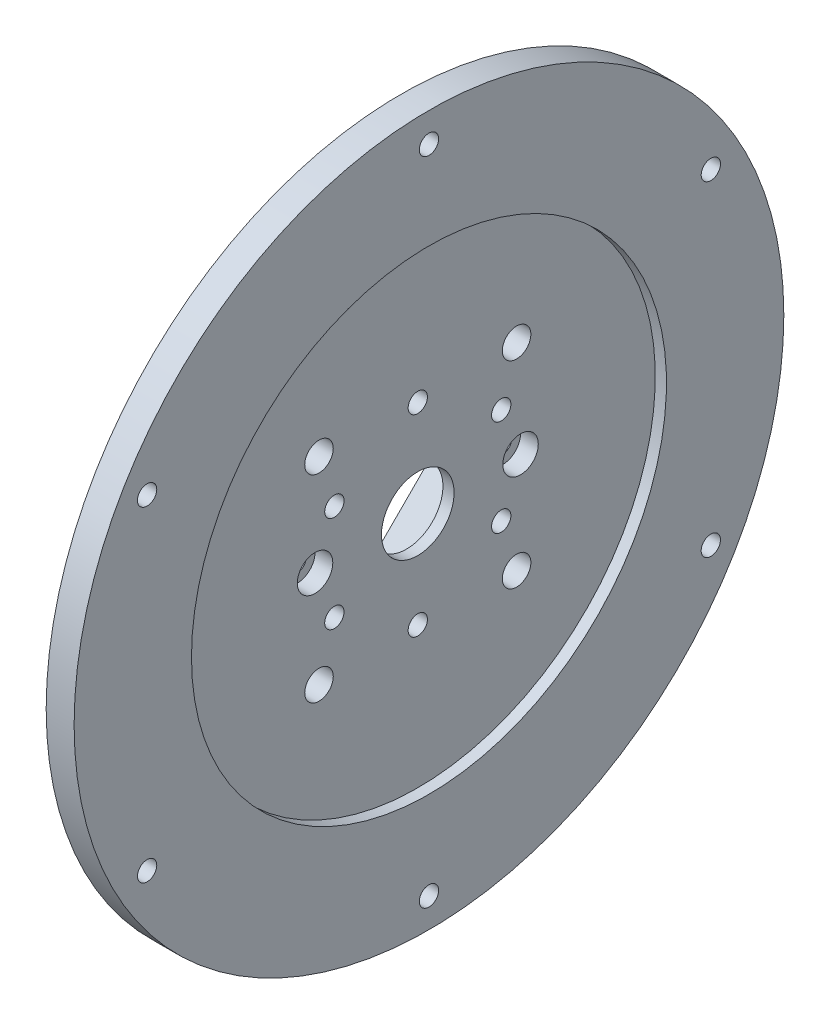
SolidWorks part; units mm, degrees
ref_plane "Front Plane" through (0, 0, 0) normal (0, 0, 1) x (1, 0, 0)
ref_plane "Top Plane" through (0, 0, 0) normal (0, 1, 0) x (1, 0, 0)
ref_plane "Right Plane" through (0, 0, 0) normal (1, 0, 0) x (0, 0, -1)
sketch "Sketch1" plane through (0, 0, 0) normal (0, 0, 1) x (1, 0, 0)
  line L0 (0, 0) -> (58.591, 0) construction
  line L2 (0, 0) -> (18.4, 0)
  line L3 (0, 0) -> (0, 2.5)
  line L4 (0, 2.5) -> (18.4, 2.5)
  line L5 (18.4, 0) -> (18.4, 2.5)
  line L6 (6, 2.5) -> (6, 6)
  line L11 (6, 6) -> (9.97, 6)
  line L16 (12.97, 6) -> (12.97, 3)
  line L17 (12.97, 3) -> (13.6304, 3)
  line L18 (13.6304, 3) -> (13.6304, 2.5)
  line L19 (13.6304, 2.5) -> (6, 2.5)
  line L22 (13.6304, 2.5) -> (16.1104, 2.5)
  line L23 (13.6304, 2.5) -> (13.6304, 4)
  line L24 (13.6304, 4) -> (16.1104, 4)
  line L25 (16.1104, 2.5) -> (16.1104, 4)
  line L27 (6, 6) -> (9.97, 6)
  line L28 (6, 6) -> (6, 9)
  line L29 (6, 9) -> (9.97, 9)
  line L30 (9.97, 6) -> (9.97, 9)
  line L31 (6, 9) -> (6, 8.25)
  line L32 (6, 8.25) -> (5, 8.25)
  line L33 (8.58, 22.001) -> (8.58, 12.476) construction
  line L34 (5, 12.476) -> (12.16, 12.476)
  line L35 (9.97, 9) -> (12.16, 9)
  line L36 (5, 7.5) -> (3, 7.5)
  line L37 (5, 8.25) -> (5, 12.476)
  line L38 (5, 7.5) -> (5, 14)
  line L39 (5, 14) -> (3, 14)
  line L40 (3, 7.5) -> (3, 14)
  line L41 (5, 22.001) -> (12.16, 22.001)
  line L42 (5, 22.001) -> (5, 30.1625)
  line L43 (5, 30.1625) -> (12.16, 30.1625)
  line L44 (12.16, 22.001) -> (12.16, 30.1625)
  line L49 (16.6304, 22.001) -> (16.6304, 7.5)
  line L51 (23.0104, 7.5) -> (23.0104, 6.5)
  line L54 (16.1104, 4) -> (13.6304, 4)
  line L56 (18.0304, 7.5) -> (23.0104, 7.5)
  line L57 (13.16, 22.001) -> (16.6304, 22.001)
  line L58 (16.1104, 3.5) -> (20.0104, 3.5)
  line L59 (29.9004, 14) -> (26.9004, 11)
  line L60 (4, 31.75) -> (18.0304, 31.75)
  line L61 (18.0304, 7.5) -> (23.0104, 7.5)
  line L62 (18.0304, 7.5) -> (18.0304, 12)
  line L63 (18.0304, 12) -> (23.0104, 12)
  line L64 (23.0104, 7.5) -> (23.0104, 12)
  line L65 (18.0304, 31.75) -> (18.0304, 12)
  line L66 (23.0104, 11) -> (26.9004, 11)
  line L67 (34.8004, 23) -> (31.3004, 19.5)
  line L68 (35.8004, 31) -> (38.7904, 33.99)
  line L69 (29.9004, 14) -> (29.9004, 15)
  line L70 (29.9004, 15) -> (22.9304, 15)
  line L71 (22.9304, 15) -> (21.0304, 15)
  line L72 (18.0304, 7.5) -> (16.6304, 7.5)
  line L73 (21.0304, 15) -> (21.0304, 43)
  line L74 (20.0304, 40) -> (10.0704, 40)
  line L75 (10.0704, 40) -> (4, 40)
  line L76 (21.0304, 43) -> (20.0304, 43)
  line L77 (22.9304, 15) -> (29.9004, 15)
  line L78 (22.9304, 15) -> (22.9304, 21)
  line L79 (22.9304, 21) -> (29.9004, 21)
  line L80 (29.9004, 15) -> (29.9004, 21)
  line L81 (10.0704, 40) -> (20.0304, 40)
  line L82 (10.0704, 40) -> (10.0704, 50)
  line L83 (10.0704, 50) -> (20.0304, 50)
  line L84 (20.0304, 40) -> (20.0304, 50)
  line L85 (4, 40) -> (4, 31.75)
  line L86 (12.97, 3) -> (12.97, 2.5)
  line L87 (31.3004, 19.5) -> (29.9004, 19.5)
  line L88 (21.51, 63.5) -> (21.51, 44)
  line L89 (21.51, 63.5) -> (25.9304, 63.5)
  line L90 (25.9304, 63.5) -> (25.9304, 25)
  line L91 (27.8304, 25) -> (25.9304, 25)
  line L92 (10.0704, 48) -> (9, 48)
  line L93 (9, 48) -> (9, 53.476)
  line L94 (9, 53.476) -> (20.0304, 53.476)
  line L95 (20.0304, 53.476) -> (20.0304, 50)
  line L96 (14.5152, 63.001) -> (14.5152, 53.476) construction
  line L97 (9, 63.001) -> (20.0304, 63.001)
  line L98 (9, 63.001) -> (9, 68.2625)
  line L99 (9, 68.2625) -> (20.0304, 68.2625)
  line L100 (20.0304, 63.001) -> (20.0304, 68.2625)
  line L101 (12.97, 6) -> (11.97, 6)
  line L102 (9, 42.5) -> (5, 42.5)
  line L103 (9, 42.5) -> (9, 55)
  line L104 (9, 55) -> (5, 55)
  line L105 (5, 42.5) -> (5, 55)
  line L106 (9.97, 6) -> (10.87, 6)
  line L107 (27.8304, 25) -> (34.8004, 25)
  line L108 (34.8004, 25) -> (34.8004, 23)
  line L109 (0, 0) -> (-2, 0)
  line L110 (0, 0) -> (0, 11)
  line L111 (27.8304, 25) -> (34.8004, 25)
  line L112 (27.8304, 25) -> (27.8304, 32.5)
  line L113 (27.8304, 32.5) -> (34.8004, 32.5)
  line L114 (34.8004, 25) -> (34.8004, 32.5)
  line L115 (35.8004, 31) -> (34.8004, 31)
  line L116 (27.8304, 32.5) -> (27.8304, 64.5)
  line L117 (21.1827, 74.025) -> (6.8477, 74.025)
  line L118 (6.8477, 74.025) -> (6.8477, 76.2)
  line L119 (38.7904, 47.29) -> (30.8304, 55.25)
  line L120 (0, 11) -> (-2, 11)
  line L121 (38.7904, 43.815) -> (30.8529, 43.815)
  line L123 (-4.8, 69.85) -> (1.55, 76.2)
  line L124 (38.7904, 47.29) -> (38.7904, 33.99)
  line L125 (-2, 0) -> (-2, 11)
  line L126 (38.7904, 37.465) -> (30.8529, 37.465)
  line L127 (30.8529, 43.815) -> (30.8529, 37.465)
  line L128 (6, 2.5) -> (6, 0)
  line L129 (0, 63.5) -> (0, 30)
  line L132 (5, 63.5) -> (0, 63.5)
  line L136 (-1.8, 30) -> (-11.76, 30)
  line L138 (-13.76, 25.4) -> (-2, 25.4)
  line L139 (-2, 25.4) -> (-2, 11.5)
  line L140 (27.8304, 64.5) -> (21.1827, 64.5)
  line L141 (-1.8, 30) -> (-11.76, 30)
  line L142 (-1.8, 30) -> (-1.8, 39)
  line L143 (-1.8, 39) -> (-11.76, 39)
  line L144 (-11.76, 30) -> (-11.76, 39)
  line L145 (21.1827, 64.5) -> (21.1827, 74.025)
  line L146 (-12.76, 37) -> (-12.76, 47.29)
  line L147 (-12.76, 37) -> (-11.76, 37)
  line L148 (30.8304, 55.25) -> (30.8304, 76.2)
  line L149 (11.97, 6) -> (11.97, 5.45)
  line L154 (-2, 11.5) -> (1, 11.5)
  line L155 (5, 60.6197) -> (24.05, 60.6197)
  line L160 (5, 60.6197) -> (5, 55.8572)
  line L161 (5, 55.8572) -> (24.05, 55.8572)
  line L166 (24.05, 60.6197) -> (24.05, 55.8572)
  line L167 (5, 60.6197) -> (24.05, 55.8572) construction
  line L172 (5, 55.8572) -> (24.05, 60.6197) construction
  line L173 (24.05, 62.2072) -> (25.9304, 62.2072)
  line L174 (11.97, 5.45) -> (10.87, 5.45)
  line L175 (10.87, 6) -> (10.87, 5.45)
  line L176 (24.05, 62.2072) -> (24.05, 54.2697)
  line L177 (24.05, 54.2697) -> (25.9304, 54.2697)
  line L178 (25.9304, 62.2072) -> (25.9304, 54.2697)
  line L179 (24.05, 62.2072) -> (25.9304, 54.2697) construction
  line L180 (24.05, 54.2697) -> (25.9304, 62.2072) construction
  line L181 (3, 19.6197) -> (15.7, 19.6197)
  line L182 (3, 19.6197) -> (3, 14.8572)
  line L183 (3, 14.8572) -> (15.7, 14.8572)
  line L184 (15.7, 19.6197) -> (15.7, 14.8572)
  line L185 (3, 19.6197) -> (15.7, 14.8572) construction
  line L186 (3, 14.8572) -> (15.7, 19.6197) construction
  line L187 (15.7, 21.2072) -> (16.6304, 21.2072)
  line L188 (15.7, 21.2072) -> (15.7, 13.2697)
  line L189 (15.7, 13.2697) -> (16.6304, 13.2697)
  line L190 (16.6304, 21.2072) -> (16.6304, 13.2697)
  line L191 (15.7, 21.2072) -> (16.6304, 13.2697) construction
  line L192 (15.7, 13.2697) -> (16.6304, 21.2072) construction
  line L193 (1, 11.5) -> (1, 6.5)
  line L194 (1, 6.5) -> (3, 6.5)
  line L195 (23.0104, 6.5) -> (20.0104, 3.5)
  line L196 (5, 63.5) -> (5, 42.5)
  line L197 (5, 42.5) -> (3, 42.5)
  line L198 (3, 42.5) -> (3, 6.5)
  line L199 (6, 0) -> (12.97, 0)
  line L200 (12.97, 0) -> (12.97, 2.5)
  line L201 (18.0304, 31.75) -> (18.0304, 35.875)
  line L202 (18.0304, 35.875) -> (21.0304, 35.875)
  line L203 (30.8304, 76.2) -> (6.8477, 76.2)
  line L204 (3.4027, 69.85) -> (7.8477, 69.85) construction
  line L205 (7.8477, 67.4687) -> (26.8977, 67.4688)
  line L206 (7.8477, 74.025) -> (7.8477, 64.5)
  line L207 (7.8477, 64.5) -> (-1.8, 64.5)
  line L208 (-1.8, 64.5) -> (-1.8, 39)
  line L209 (-12.76, 47.29) -> (-4.8, 55.25)
  line L210 (-4.8, 55.25) -> (-4.8, 69.85)
  line L211 (7.8477, 67.4687) -> (7.8477, 72.2313)
  line L212 (7.8477, 72.2313) -> (26.8977, 72.2313)
  line L213 (26.8977, 67.4688) -> (26.8977, 72.2313)
  line L214 (26.8977, 73.8187) -> (30.8304, 73.8187)
  line L215 (26.8977, 73.8187) -> (26.8977, 65.8813)
  line L216 (26.8977, 65.8813) -> (30.8304, 65.8813)
  line L217 (30.8304, 73.8187) -> (30.8304, 65.8813)
  line L218 (3.4027, 72.2313) -> (25.6277, 72.2313)
  line L219 (3.4027, 72.2313) -> (3.4027, 67.4687)
  line L220 (3.4027, 67.4687) -> (25.6277, 67.4687)
  line L221 (25.6277, 72.2313) -> (25.6277, 67.4687)
  line L222 (25.6277, 69.85) -> (21.1827, 69.85) construction
  line L223 (21.51, 44) -> (22.9304, 44)
  line L224 (22.9304, 44) -> (22.9304, 21)
  line L225 (13.6304, 4) -> (13.6304, 12.2697)
  line L226 (13.6304, 12.2697) -> (13.16, 12.2697)
  line L227 (13.16, 12.2697) -> (13.16, 22.001)
  line L228 (12.16, 9) -> (12.16, 12.476)
  line L229 (-1.8, 30) -> (0, 30)
  line L230 (9, 65.6317) -> (3.4027, 65.6317) construction
  line L231 (20.0304, 65.6317) -> (25.6277, 65.6317) construction
  line L232 (1.55, 76.2) -> (6.8477, 76.2)
  line L233 (-11.76, 30) -> (-13.76, 30)
  line L234 (-13.76, 30) -> (-13.76, 25.4)
  circle A0 centre (26.8804, 25.95) radius 0.95
  circle A1 centre (21.9804, 15.95) radius 0.95
  circle A2 centre (17.3304, 8.2) radius 0.7
  circle A3 centre (10.42, 6.45) radius 0.45
  circle A4 centre (-0.9, 30.9) radius 0.9
  point P7 (24.9902, 58.2385)
  point P131 (16.1652, 17.2385)
  point P135 (14.525, 58.2385)
  point P146 (9.35, 17.2385)
sketch "Sketch2" plane through (0, 0, 0) normal (0, 0, 1) x (1, 0, 0)
  line L0 (-1.8, 30) -> (-11.76, 30) construction
  line L1 (-2, 25.4) -> (-2, 11.5) construction
  line L3 (-13.76, 25.4) -> (-2, 25.4) construction
  line L4 (-2, 11.5) -> (1, 11.5) construction
  line L5 (1, 11.5) -> (1, 6.5) construction
  line L6 (1, 6.5) -> (3, 6.5) construction
  line L7 (3, 42.5) -> (3, 6.5) construction
  line L8 (5, 42.5) -> (3, 42.5) construction
  line L9 (5, 63.5) -> (5, 42.5) construction
  line L10 (5, 63.5) -> (0, 63.5) construction
  line L11 (0, 63.5) -> (0, 30) construction
  line L14 (-1.8, 30) -> (-11.76, 30)
  line L15 (-2, 25.4) -> (-2, 11.5)
  line L17 (-13.76, 25.4) -> (-2, 25.4)
  line L18 (-2, 11.5) -> (1, 11.5)
  line L19 (1, 11.5) -> (1, 6.5)
  line L20 (1, 6.5) -> (3, 6.5)
  line L21 (3, 42.5) -> (3, 6.5)
  line L22 (5, 42.5) -> (3, 42.5)
  line L23 (5, 63.5) -> (5, 42.5)
  line L24 (5, 63.5) -> (0, 63.5)
  line L25 (0, 63.5) -> (0, 30)
  line L28 (-1.8, 30) -> (0, 30) construction
  line L29 (-1.8, 30) -> (0, 30)
  line L30 (-13.76, 30) -> (-13.76, 25.4) construction
  line L31 (-11.76, 30) -> (-13.76, 30) construction
  line L32 (-13.76, 30) -> (-13.76, 25.4)
  line L33 (-11.76, 30) -> (-13.76, 30)
revolve "Revolve1" add sketch "Sketch2" angle 360 about L0 region at (-0.9, 29.3999, 0)
sketch "Sketch3" plane through (0, 0, 0) normal (1, 0, 0) x (0, 0, -1)
  line L0 (0, 0) -> (0, 69.85) construction
  line L1 (0, 0) -> (13.6271, 68.5079) construction
  line L2 (0, 0) -> (0, 58.2385) construction
  line L3 (0, 0) -> (50.436, 29.1192) construction
  line L4 (0, 0) -> (0, 31.75) construction
  line L5 (0, 0) -> (12.1502, 29.3332) construction
  line L6 (0, 0) -> (0, 17.2385) construction
  line L7 (0, 0) -> (14.929, 8.6192) construction
  line L8 (0, 0) -> (0, 58.2385) construction
  line L9 (0, 0) -> (50.436, 29.1192) construction
  line L10 (0, 0) -> (5.9583, 29.9542) construction
  line L11 (0, 0) -> (16.9677, 25.394) construction
  circle A0 centre (0, 0) radius 69.85 construction
  circle A1 centre (0, 0) radius 58.2385 construction
  circle A2 centre (0, 0) radius 31.75 construction
  circle A3 centre (0, 0) radius 17.2385 construction
  circle A4 centre (0, 69.85) radius 3.175
  circle A5 centre (0, 58.2385) radius 4.7625
  circle A6 centre (0, 31.75) radius 3.175
  circle A7 centre (0, 17.2385) radius 4.7625
  circle A8 centre (13.6271, 68.5079) radius 3.175
  circle A9 centre (26.7304, 64.533) radius 3.175
  circle A10 centre (38.8066, 58.0782) radius 3.175
  circle A11 centre (49.3914, 49.3914) radius 3.175
  circle A12 centre (58.0782, 38.8066) radius 3.175
  circle A13 centre (64.533, 26.7304) radius 3.175
  circle A14 centre (68.5079, 13.6271) radius 3.175
  circle A15 centre (69.85, 0) radius 3.175
  circle A16 centre (68.5079, -13.6271) radius 3.175
  circle A17 centre (64.533, -26.7304) radius 3.175
  circle A18 centre (58.0782, -38.8066) radius 3.175
  circle A19 centre (49.3914, -49.3914) radius 3.175
  circle A20 centre (38.8066, -58.0782) radius 3.175
  circle A21 centre (26.7304, -64.533) radius 3.175
  circle A22 centre (13.6271, -68.5079) radius 3.175
  circle A23 centre (0, -69.85) radius 3.175
  circle A24 centre (-13.6271, -68.5079) radius 3.175
  circle A25 centre (-26.7304, -64.533) radius 3.175
  circle A26 centre (-38.8066, -58.0782) radius 3.175
  circle A27 centre (-49.3914, -49.3914) radius 3.175
  circle A28 centre (-58.0782, -38.8066) radius 3.175
  circle A29 centre (-64.533, -26.7304) radius 3.175
  circle A30 centre (-68.5079, -13.6271) radius 3.175
  circle A31 centre (-69.85, 0) radius 3.175
  circle A32 centre (-68.5079, 13.6271) radius 3.175
  circle A33 centre (-64.533, 26.7304) radius 3.175
  circle A34 centre (-58.0782, 38.8066) radius 3.175
  circle A35 centre (-49.3914, 49.3914) radius 3.175
  circle A36 centre (-38.8066, 58.0782) radius 3.175
  circle A37 centre (-26.7304, 64.533) radius 3.175
  circle A38 centre (-13.6271, 68.5079) radius 3.175
  circle A47 centre (50.436, 29.1192) radius 4.7625
  circle A48 centre (50.436, -29.1192) radius 4.7625
  circle A49 centre (0, -58.2385) radius 4.7625
  circle A50 centre (-50.436, -29.1192) radius 4.7625
  circle A51 centre (-50.436, 29.1192) radius 4.7625
  circle A58 centre (12.1502, 29.3332) radius 3.175
  circle A59 centre (22.4506, 22.4506) radius 3.175
  circle A60 centre (29.3332, 12.1502) radius 3.175
  circle A61 centre (31.75, 0) radius 3.175
  circle A62 centre (29.3332, -12.1502) radius 3.175
  circle A63 centre (22.4506, -22.4506) radius 3.175
  circle A64 centre (12.1502, -29.3332) radius 3.175
  circle A65 centre (0, -31.75) radius 3.175
  circle A66 centre (-12.1502, -29.3332) radius 3.175
  circle A67 centre (-22.4506, -22.4506) radius 3.175
  circle A68 centre (-29.3332, -12.1502) radius 3.175
  circle A69 centre (-31.75, 0) radius 3.175
  circle A70 centre (-29.3332, 12.1502) radius 3.175
  circle A71 centre (-22.4506, 22.4506) radius 3.175
  circle A72 centre (14.929, 8.6192) radius 4.7625
  circle A73 centre (14.929, -8.6192) radius 4.7625
  circle A74 centre (0, -17.2385) radius 4.7625
  circle A75 centre (-14.929, -8.6192) radius 4.7625
  circle A76 centre (-14.929, 8.6192) radius 4.7625
  circle A77 centre (0, 0) radius 50
  circle A78 centre (0, 0) radius 9
  circle A79 centre (-12.1502, 29.3332) radius 3.175
  circle A80 centre (0, 0) radius 76.2
  circle A81 centre (0, 0) radius 74.025
  circle A82 centre (0, 69.85) radius 3.9687
  circle A83 centre (49.3914, 49.3914) radius 3.9687
  circle A84 centre (69.85, 0) radius 3.9688
  circle A85 centre (49.3914, -49.3914) radius 3.9687
  circle A86 centre (0, -69.85) radius 3.9687
  circle A87 centre (-49.3914, -49.3914) radius 3.9687
  circle A88 centre (-69.85, 0) radius 3.9688
  circle A89 centre (-49.3914, 49.3914) radius 3.9687
  circle A90 centre (0, 69.85) radius 2.3812
  circle A91 centre (13.6271, 68.5079) radius 2.3812
  circle A92 centre (26.7304, 64.533) radius 2.3813
  circle A93 centre (38.8066, 58.0782) radius 2.3812
  circle A94 centre (49.3914, 49.3914) radius 2.3812
  circle A95 centre (58.0782, 38.8066) radius 2.3812
  circle A96 centre (64.533, 26.7304) radius 2.3813
  circle A97 centre (68.5079, 13.6271) radius 2.3813
  circle A98 centre (69.85, 0) radius 2.3813
  circle A99 centre (68.5079, -13.6271) radius 2.3813
  circle A100 centre (64.533, -26.7304) radius 2.3813
  circle A101 centre (58.0782, -38.8066) radius 2.3812
  circle A102 centre (49.3914, -49.3914) radius 2.3812
  circle A103 centre (38.8066, -58.0782) radius 2.3812
  circle A104 centre (26.7304, -64.533) radius 2.3813
  circle A105 centre (13.6271, -68.5079) radius 2.3812
  circle A106 centre (0, -69.85) radius 2.3812
  circle A107 centre (-13.6271, -68.5079) radius 2.3812
  circle A108 centre (-26.7304, -64.533) radius 2.3813
  circle A109 centre (-38.8066, -58.0782) radius 2.3812
  circle A110 centre (-49.3914, -49.3914) radius 2.3812
  circle A111 centre (-58.0782, -38.8066) radius 2.3812
  circle A112 centre (-64.533, -26.7304) radius 2.3812
  arc A113 (3.0399, 30.8338) -> (8.9911, 29.65) centre (5.9583, 29.9542) cw
  arc A114 (14.6081, 27.3234) -> (19.6532, 23.9523) centre (16.9677, 25.394) cw
  arc A115 (23.9523, 19.6532) -> (27.3234, 14.6081) centre (25.394, 16.9677) cw
  arc A116 (29.65, 8.9911) -> (30.8338, 3.0399) centre (29.9542, 5.9583) cw
  arc A117 (30.8338, -3.0399) -> (29.65, -8.9911) centre (29.9542, -5.9583) cw
  arc A118 (27.3234, -14.6081) -> (23.9523, -19.6532) centre (25.394, -16.9677) cw
  arc A119 (19.6532, -23.9523) -> (14.6081, -27.3234) centre (16.9677, -25.394) cw
  arc A120 (8.9911, -29.65) -> (3.0399, -30.8338) centre (5.9583, -29.9542) cw
  arc A121 (-3.0399, -30.8338) -> (-8.9911, -29.65) centre (-5.9583, -29.9542) cw
  arc A122 (-14.6081, -27.3234) -> (-19.6532, -23.9523) centre (-16.9677, -25.394) cw
  arc A123 (-23.9523, -19.6532) -> (-27.3234, -14.6081) centre (-25.394, -16.9677) cw
  arc A124 (-29.65, -8.9911) -> (-30.8338, -3.0399) centre (-29.9542, -5.9583) cw
  arc A125 (-30.8338, 3.0399) -> (-29.65, 8.9911) centre (-29.9542, 5.9583) cw
  arc A126 (-27.3234, 14.6081) -> (-23.9523, 19.6532) centre (-25.394, 16.9677) cw
  arc A127 (-19.6532, 23.9523) -> (-14.6081, 27.3234) centre (-16.9677, 25.394) cw
  arc A128 (-8.9911, 29.65) -> (-3.0399, 30.8338) centre (-5.9583, 29.9542) cw
  arc A129 (26.9875, 0) -> (26.9932, 0.1932) centre (30.2705, 0) cw
  arc A130 (65.0988, 0.2771) -> (65.0875, 0) centre (68.4964, 0) ccw
  circle A131 centre (1.5875, 0) radius 40
  circle A132 centre (1.5875, 0) radius 2.5
  circle A133 centre (1.5875, 0) radius 3
  circle A134 centre (1.5875, 0) radius 43
  circle A135 centre (-68.5079, -13.6271) radius 2.3813
  circle A136 centre (-69.85, 0) radius 2.3813
  circle A137 centre (-68.5079, 13.6271) radius 2.3813
  circle A138 centre (-64.533, 26.7304) radius 2.3812
  circle A139 centre (-58.0782, 38.8066) radius 2.3812
  circle A140 centre (-49.3914, 49.3914) radius 2.3812
  circle A141 centre (-38.8066, 58.0782) radius 2.3812
  circle A142 centre (-26.7304, 64.533) radius 2.3813
  circle A143 centre (-13.6271, 68.5079) radius 2.3812
  circle A144 centre (0, 58.2385) radius 2.3812
  circle A145 centre (0, 58.2385) radius 3.9688
  circle A146 centre (50.436, 29.1192) radius 3.9688
  circle A147 centre (50.436, 29.1192) radius 2.3813
  circle A148 centre (50.436, -29.1192) radius 3.9687
  circle A149 centre (50.436, -29.1192) radius 2.3812
  circle A150 centre (0, -58.2385) radius 3.9687
  circle A151 centre (0, -58.2385) radius 2.3812
  circle A152 centre (-50.436, -29.1192) radius 3.9687
  circle A153 centre (-50.436, -29.1192) radius 2.3812
  circle A154 centre (-50.436, 29.1192) radius 3.9687
  circle A155 centre (-50.436, 29.1192) radius 2.3812
  spline S1 degree 4 number of poles 499 (26.9875, 0) -> (26.9932, 0.1932)
  spline S3 degree 4 number of poles 617 (65.0875, 0) -> (65.0988, 0.2771)
  point P116 (0, 0)
  point P225 (0, 0)
sketch "Sketch4" plane through (0, 0, 0) normal (1, 0, 0) x (0, 0, -1)
  circle A0 centre (-14.929, -8.6192) radius 4.7625 construction
  circle A1 centre (-14.929, 8.6192) radius 4.7625 construction
  circle A2 centre (0, 17.2385) radius 4.7625 construction
  circle A3 centre (14.929, 8.6192) radius 4.7625 construction
  circle A4 centre (14.929, -8.6192) radius 4.7625 construction
  circle A5 centre (0, -17.2385) radius 4.7625 construction
  circle A6 centre (0, -58.2385) radius 4.7625 construction
  circle A7 centre (-50.436, -29.1192) radius 4.7625 construction
  circle A8 centre (50.436, -29.1192) radius 4.7625 construction
  circle A9 centre (50.436, 29.1192) radius 4.7625 construction
  circle A10 centre (0, 58.2385) radius 4.7625 construction
  circle A11 centre (-50.436, 29.1192) radius 4.7625 construction
  circle A12 centre (-14.929, -8.6192) radius 4.7625
  circle A13 centre (-14.929, 8.6192) radius 4.7625
  circle A14 centre (0, 17.2385) radius 4.7625
  circle A15 centre (14.929, 8.6192) radius 4.7625
  circle A16 centre (14.929, -8.6192) radius 4.7625
  circle A17 centre (0, -17.2385) radius 4.7625
  circle A18 centre (0, -58.2385) radius 4.7625
  circle A19 centre (-50.436, -29.1192) radius 4.7625
  circle A20 centre (50.436, -29.1192) radius 4.7625
  circle A21 centre (50.436, 29.1192) radius 4.7625
  circle A22 centre (0, 58.2385) radius 4.7625
  circle A23 centre (-50.436, 29.1192) radius 4.7625
  circle A24 centre (0, 58.2385) radius 1.7272
  circle A25 centre (50.436, 29.1192) radius 1.7272
  circle A26 centre (50.436, -29.1192) radius 1.7272
  circle A27 centre (0, -58.2385) radius 1.7272
  circle A28 centre (-50.436, -29.1192) radius 1.7272
  circle A29 centre (-50.436, 29.1192) radius 1.7272
  circle A30 centre (-14.929, 8.6192) radius 1.7272
  circle A31 centre (0, 17.2385) radius 1.7272
  circle A32 centre (14.929, 8.6192) radius 1.7272
  circle A33 centre (14.929, -8.6192) radius 1.7272
  circle A34 centre (0, -17.2385) radius 1.7272
  circle A35 centre (-14.929, -8.6192) radius 1.7272
  dimension "D1" = 3.4544
extrude "Cut-Extrude1" cut sketch "Sketch4" against normal through all and the other way through all contours A29 | A30 | A31 | A32 | A33 | A34 | A35 | A25 | A26 | A24 | A28 | A27
sketch "Sketch5" plane through (3, 0, 0) normal (1, 0, 0) x (0, 0, -1)
  line L0 (-18.385, 0) -> (0, 0) construction
  line L1 (0, 0) -> (18.385, 0) construction
  circle A0 centre (-18.385, 0) radius 1.5875
  circle A1 centre (18.385, 0) radius 1.5875
  dimension "D2" = 3.175
  dimension "D1" = 36.77
extrude "Cut-Extrude2" cut sketch "Sketch5" against normal through all
sketch "Sketch6" plane through (3, 0, 0) normal (1, 0, 0) x (0, 0, -1)
  circle A0 centre (-18.385, 0) radius 3.175
  circle A1 centre (18.385, 0) radius 3.175
  dimension "D1" = 6.35
extrude "Cut-Extrude3" cut sketch "Sketch6" against normal blind 3.175
sketch "Sketch7" plane through (-13.76, 0, 0) normal (-1, 0, 0) x (0, 0, 1)
  line L0 (3.0706, 25.2137) -> (25.2137, 3.0706)
  line L1 (25.2137, -3.0706) -> (3.0706, -25.2137)
  line L2 (-3.0706, -25.2137) -> (-25.2137, -3.0706)
  line L3 (-25.2137, 3.0706) -> (-3.0706, 25.2137)
  circle A3 centre (0, 0) radius 25.4 construction
  circle A4 centre (0, 0) radius 25.4
  point P15 (0, 0)
  circle M5 centre (0, 0) radius 25.4
  dimension "D2" = 40
  dimension "D1" = 4
extrude "Boss-Extrude1" add sketch "Sketch7" against normal up to next contours L0 M5 | L3 M5 | L2 M5 | L1 M5 region at (-13.76, 15.6843, 15.6843) region at (-13.76, 15.6843, -15.6843) region at (-13.76, -15.6843, 15.6843) region at (-13.76, -15.6843, -15.6843)
fillet "Fillet1" radius 3.175 8 edges at (-7.88, -25.2137, -3.0706) (-7.88, -25.2137, 3.0706) (-7.88, -3.0706, 25.2137) (-7.88, 3.0706, 25.2137) (-7.88, -3.0706, -25.2137) (-7.88, 3.0706, -25.2137) (-7.88, 25.2137, 3.0706) (-7.88, 25.2137, -3.0706)
sketch "Sketch8" plane through (-13.76, 0, 0) normal (-1, 0, 0) x (0, 0, 1)
  line L0 (0, 0) -> (17.6777, 17.6777) construction
  line L1 (0, 0) -> (13.9248, 0) construction
  line L2 (17.6777, 17.6777) -> (21.2132, 21.2132) construction
  line L3 (17.6777, 17.6777) -> (14.1421, 14.1421) construction
  line L7 (3.874, 24.4103) -> (24.4103, 3.874) construction
  circle A0 centre (17.6777, 17.6777) radius 2.5527
  circle A1 centre (0, 0) radius 30 construction
  circle A2 centre (17.6777, -17.6777) radius 2.5527
  circle A3 centre (-17.6777, -17.6777) radius 2.5527
  circle A4 centre (-17.6777, 17.6777) radius 2.5527
  point P20 (0, 0)
  dimension "D2" = 5.1054
  dimension "D1" = 45
  dimension "D3" = 4
extrude "Cut-Extrude4" cut sketch "Sketch8" against normal through all
